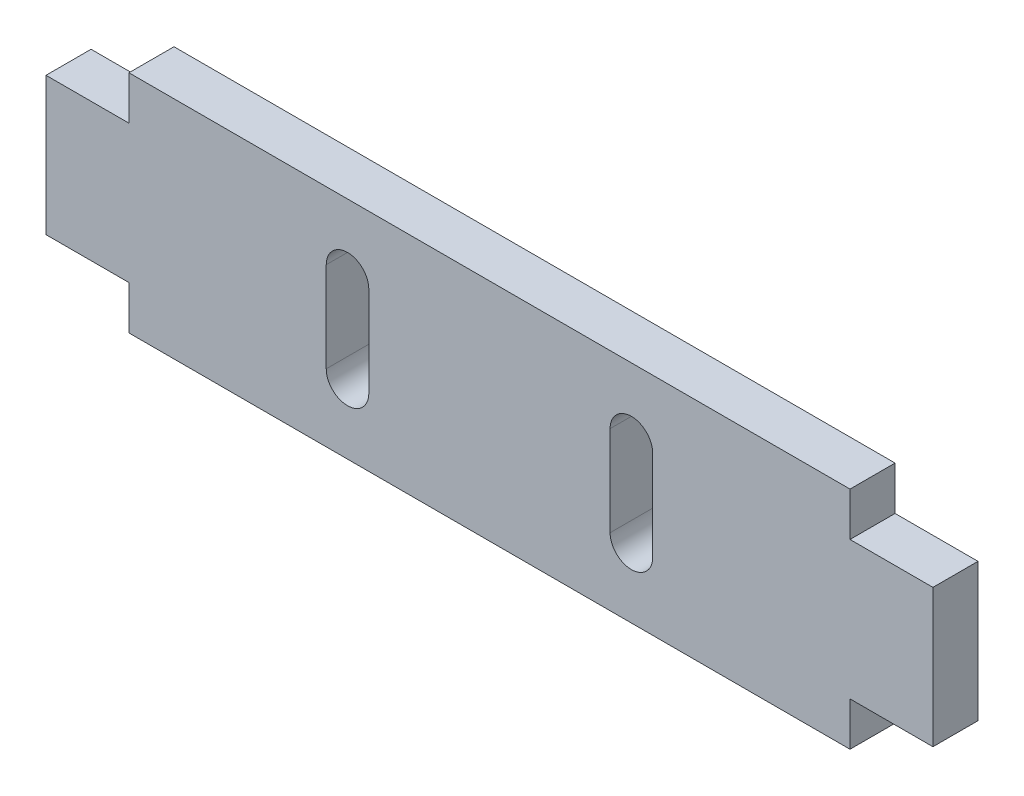
SolidWorks part; units mm, degrees
ref_plane "Front Plane" through (0, 0, 0) normal (0, 0, 1) x (1, 0, 0)
ref_plane "Top Plane" through (0, 0, 0) normal (0, 1, 0) x (1, 0, 0)
ref_plane "Right Plane" through (0, 0, 0) normal (1, 0, 0) x (0, 0, -1)
sketch "Sketch1" plane through (0, 0, 0) normal (0, 0, 1) x (1, 0, 0)
  line L0 (25.4, 0) -> (-25.4, 0) construction
  line L1 (-25.4, -7.9375) -> (25.4, -7.9375)
  line L2 (0, 7.9375) -> (0, -7.9375) construction
  line L3 (-25.4, 7.9375) -> (25.4, 7.9375)
  line L4 (25.4, -7.9375) -> (25.4, -4.8625)
  line L5 (-25.4, -7.9375) -> (25.4, 7.9375) construction
  line L6 (-25.4, 7.9375) -> (25.4, -7.9375) construction
  line L7 (25.4, 4.8625) -> (25.4, 7.9375)
  line L8 (31.242, -4.8625) -> (25.4, -4.8625)
  line L9 (31.242, -4.8625) -> (31.242, 4.8625)
  line L10 (31.242, 4.8625) -> (25.4, 4.8625)
  line L11 (-31.242, 4.8625) -> (-25.4, -4.8625) construction
  line L12 (31.242, -4.8625) -> (25.4, 4.8625) construction
  line L13 (31.242, 4.8625) -> (25.4, -4.8625) construction
  line L14 (-31.242, -4.8625) -> (-25.4, 4.8625) construction
  line L15 (-31.242, 4.8625) -> (-25.4, 4.8625)
  line L16 (-31.242, -4.8625) -> (-31.242, 4.8625)
  line L17 (-31.242, -4.8625) -> (-25.4, -4.8625)
  line L18 (-25.4, 4.8625) -> (-25.4, 7.9375)
  line L19 (-25.4, -7.9375) -> (-25.4, -4.8625)
  line L20 (-10, -3.175) -> (-10, 3.175) construction
  line L21 (-11.5, -3.175) -> (-11.5, 3.175)
  line L22 (-8.5, -3.175) -> (-8.5, 3.175)
  line L23 (10, -3.175) -> (10, 3.175) construction
  line L24 (11.5, -3.175) -> (11.5, 3.175)
  line L25 (8.5, -3.175) -> (8.5, 3.175)
  arc A0 (-11.5, -3.175) -> (-8.5, -3.175) centre (-10, -3.175) ccw
  arc A1 (-8.5, 3.175) -> (-11.5, 3.175) centre (-10, 3.175) ccw
  arc A2 (11.5, -3.175) -> (8.5, -3.175) centre (10, -3.175) cw
  arc A3 (8.5, 3.175) -> (11.5, 3.175) centre (10, 3.175) cw
  point P0 (0, 0)
  point P8 (28.321, 0)
  point P19 (-28.321, 0)
  point P22 (-10, 0)
  point P29 (10, 0)
  dimension "D5" = 1.5
  dimension "D1" = 50.8
  dimension "D2" = 15.875
  dimension "D3" = 5.842
  dimension "D4" = 9.725
  dimension "D6" = 6.35
  dimension "D7" = 10
extrude "Boss-Extrude1" add sketch "Sketch1" along normal blind 3.175
